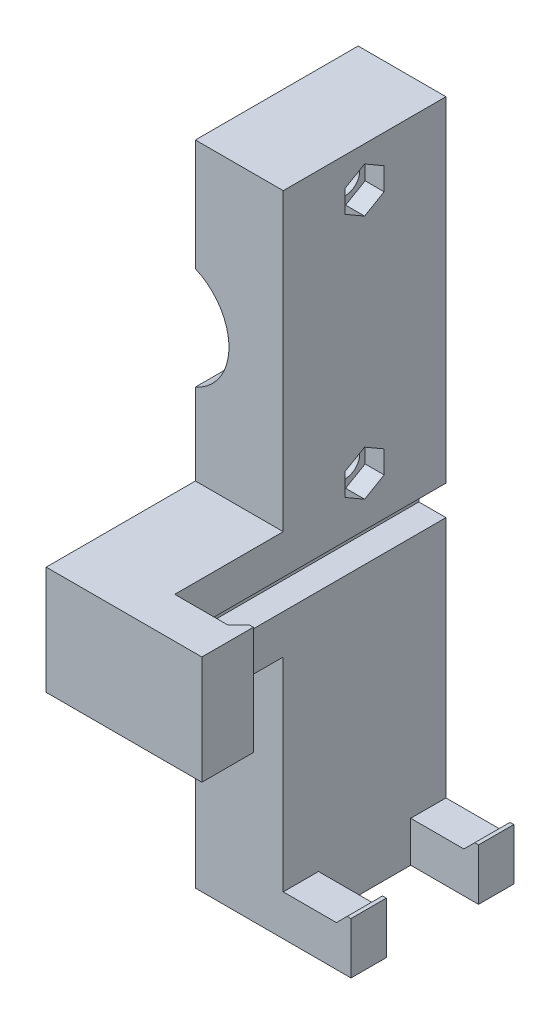
SolidWorks part; units mm, degrees
ref_plane "Plan de face" through (0, 0, 0) normal (0, 0, 1) x (1, 0, 0)
ref_plane "Plan de dessus" through (0, 0, 0) normal (0, 1, 0) x (1, 0, 0)
ref_plane "Plan de droite" through (0, 0, 0) normal (1, 0, 0) x (0, 0, -1)
sketch "Esquisse1" plane through (0, 0, 0) normal (0, 0, 1) x (1, 0, 0)
  line L0 (4.1105, 33.2262) -> (4.1105, -27.5499) construction
  line L1 (4.1105, 9.4443) -> (4.1105, 30)
  line L2 (4.1105, -9.4443) -> (4.1105, -89.4443)
  line L3 (4.1105, -89.4443) -> (32.8, -89.4443)
  line L4 (32.8, -89.4443) -> (32.8, -81.9443)
  line L5 (32.8, -81.9443) -> (20.3, -81.9443)
  line L6 (20.3, -81.9443) -> (20.3, 30)
  line L7 (20.3, 30) -> (4.1105, 30)
  arc A0 (4.1105, 9.4443) -> (4.1105, -9.4443) centre (0, 0) cw
  dimension "D1" = 10.3
  dimension "D3" = 20.3
  dimension "D2" = 80
  dimension "D4" = 7.5
  dimension "D5" = 12.5
  dimension "D6" = 30
extrude "Boss.-Extru.1" add sketch "Esquisse1" along normal blind 30
sketch "Esquisse3" plane through (4.1105, 0, 0) normal (-1, 0, 0) x (0, 0, 1)
  line L0 (15, 22.6) -> (15, -22.6) construction
  line L5 (30, 0) -> (0, 0) construction
  circle A0 centre (15, 22.6) radius 2.6
  circle A1 centre (15, -22.6) radius 2.6
  dimension "D1" = 5.2
  dimension "D2" = 22.6
  dimension "D3" = 45.2
extrude "Enlèv. mat.-Extru.1" cut sketch "Esquisse3" against normal blind 30
sketch "Esquisse4" plane through (20.3, 0, 0) normal (1, 0, 0) x (0, 0, -1)
  line L1 (-15, -18.4431) -> (-18.6, -20.5215)
  line L2 (-18.6, -20.5215) -> (-18.6, -24.6785)
  line L3 (-18.6, -24.6785) -> (-15, -26.7569)
  line L4 (-15, -26.7569) -> (-11.4, -24.6785)
  line L5 (-11.4, -24.6785) -> (-11.4, -20.5215)
  line L6 (-11.4, -20.5215) -> (-15, -18.4431)
  line L7 (-15, 26.7569) -> (-18.6, 24.6785)
  line L8 (-18.6, 24.6785) -> (-18.6, 20.5215)
  line L9 (-18.6, 20.5215) -> (-15, 18.4431)
  line L10 (-15, 18.4431) -> (-11.4, 20.5215)
  line L11 (-11.4, 20.5215) -> (-11.4, 24.6785)
  line L12 (-11.4, 24.6785) -> (-15, 26.7569)
  circle A0 centre (-15, -22.6) radius 3.6 construction
  circle A1 centre (-15, 22.6) radius 3.6 construction
  dimension "D1" = 7.2
extrude "Enlèv. mat.-Extru.2" cut sketch "Esquisse4" against normal blind 3.5
sketch "Esquisse6" plane through (0, 0, 30) normal (0, 0, 1) x (1, 0, 0)
  line L0 (4.1105, -9.4443) -> (4.1105, -89.4443) construction
  line L1 (4.1105, -24.4443) -> (20.3, -24.4443)
  line L2 (4.1105, -24.4443) -> (4.1105, -44.4443)
  line L3 (4.1105, -44.4443) -> (20.3, -44.4443)
  line L4 (20.3, -24.4443) -> (20.3, -44.4443)
  line L5 (20.3, -81.9443) -> (20.3, 30) construction
  line L6 (4.1105, -89.4443) -> (32.8, -89.4443) construction
  dimension "D1" = 20
  dimension "D2" = 45
extrude "Boss.-Extru.2" add sketch "Esquisse6" along normal blind 27.5
sketch "Esquisse7" plane through (20.3, 0, 0) normal (1, 0, 0) x (0, 0, -1)
  line L0 (-57.5, -44.4443) -> (-30, -44.4443) construction
  line L1 (-57.5, -24.4443) -> (-50, -24.4443)
  line L2 (-57.5, -24.4443) -> (-57.5, -44.4443)
  line L3 (-57.5, -44.4443) -> (-50, -44.4443)
  line L4 (-50, -24.4443) -> (-50, -44.4443)
  dimension "D1" = 7.5
extrude "Boss.-Extru.3" add sketch "Esquisse7" along normal blind 12.5
sketch "Esquisse9" plane through (20.3, 0, 0) normal (1, 0, 0) x (0, 0, -1)
  line L0 (-50, -34.4443) -> (0, -34.4443) construction
  line L1 (-50, -44.4443) -> (-50, -24.4443) construction
  line L2 (0, -81.9443) -> (0, 30) construction
  line L4 (0, -31.6943) -> (-45, -31.6943)
  line L5 (0, -31.6943) -> (0, -37.1943)
  line L6 (0, -37.1943) -> (-45, -37.1943)
  line L7 (-45, -31.6943) -> (-45, -37.1943)
  circle A0 centre (-43, -34.4443) radius 1
  dimension "D4" = 2
  dimension "D5" = 2
  dimension "D1" = 45
  dimension "D2" = 5.5
  dimension "D3" = 2.75
extrude "Enlèv. mat.-Extru.4" cut sketch "Esquisse9" against normal blind 5
sketch "Esquisse10" plane through (20.3, 0, 0) normal (1, 0, 0) x (0, 0, -1)
  circle A0 centre (-43, -34.4443) radius 1.5
  dimension "D1" = 3
extrude "Boss.-Extru.4" add sketch "Esquisse10" against normal blind 1.4
chamfer "Chanfrein1" distance 1 angle 45 1 edges at (18.9, -34.4443, 41.5)
sketch "Esquisse11" plane through (0, 0, 0) normal (0, 0, -1) x (-1, 0, 0)
  line L0 (-15.3, -34.4443) -> (-4.1105, -34.4443) construction
  line L1 (-15.3, -37.1943) -> (-15.3, -31.6943) construction
  line L2 (-4.1105, -9.4443) -> (-4.1105, -89.4443) construction
  line L3 (-12.1105, -32.6943) -> (-7.1105, -32.6943)
  line L4 (-7.1105, -32.6943) -> (-4.8502, -34.4443)
  line L5 (-4.8502, -34.4443) -> (-7.1105, -36.1943)
  line L6 (-7.1105, -36.1943) -> (-12.1105, -36.1943)
  line L7 (-12.1105, -36.1943) -> (-14.3707, -34.4443)
  line L8 (-14.3707, -34.4443) -> (-12.1105, -32.6943)
  point P8 (-9.6105, -32.6943)
  dimension "D1" = 5
  dimension "D2" = 3.5
  dimension "D3" = 5.5
extrude "Enlèv. mat.-Extru.5" cut sketch "Esquisse11" against normal blind 25
sketch "Esquisse12" plane through (0, 0, 50) normal (0, 0, -1) x (-1, 0, 0)
  line L0 (-32.8, -44.4443) -> (-20.3, -44.4443) construction
  line L1 (-32.8, -24.4443) -> (-30.1, -24.4443)
  line L2 (-32.8, -24.4443) -> (-32.8, -44.4443)
  line L3 (-32.8, -44.4443) -> (-30.1, -44.4443)
  line L4 (-30.1, -24.4443) -> (-30.1, -44.4443)
  line L6 (-20.3, -44.4443) -> (-20.3, -24.4443) construction
  dimension "D1" = 9.8
extrude "Boss.-Extru.5" add sketch "Esquisse12" along normal blind 2
chamfer "Chanfrein2" distance 2 angle 45 1 edges at (30.1, -34.4443, 48)
sketch "Esquisse13" plane through (0, -81.9443, 0) normal (0, 1, 0) x (1, 0, 0)
  line L0 (32.8, -30) -> (20.3, -30) construction
  line L1 (32.8, 0) -> (30.1, 0)
  line L2 (32.8, 0) -> (32.8, -30)
  line L3 (32.8, -30) -> (30.1, -30)
  line L4 (30.1, 0) -> (30.1, -30)
  line L5 (20.3, -30) -> (20.3, 0) construction
  dimension "D1" = 9.8
extrude "Boss.-Extru.6" add sketch "Esquisse13" along normal blind 2
chamfer "Chanfrein3" distance 2 angle 45 1 edges at (30.1, -79.9443, 15)
sketch "Esquisse15" plane through (32.8, 0, 0) normal (1, 0, 0) x (0, 0, -1)
  line L0 (-15, -79.9443) -> (-15, -89.4443) construction
  line L1 (-30, -79.9443) -> (0, -79.9443) construction
  line L2 (-30, -89.4443) -> (0, -89.4443) construction
  line L3 (-30, -89.4443) -> (-30, -79.9443) construction
  line L4 (-23.5, -89.4443) -> (-6.5, -89.4443)
  line L5 (-23.5, -89.4443) -> (-23.5, -79.9443)
  line L6 (-23.5, -79.9443) -> (-6.5, -79.9443)
  line L7 (-6.5, -89.4443) -> (-6.5, -79.9443)
  line L8 (-23.5, -89.4443) -> (-6.5, -79.9443) construction
  line L9 (-23.5, -79.9443) -> (-6.5, -89.4443) construction
  point P6 (-15, -84.6943)
  dimension "D1" = 6.5
extrude "Enlèv. mat.-Extru.6" cut sketch "Esquisse15" against normal up to surface (12.5 mm away) up to face at (20.3, 22.6, 15)
